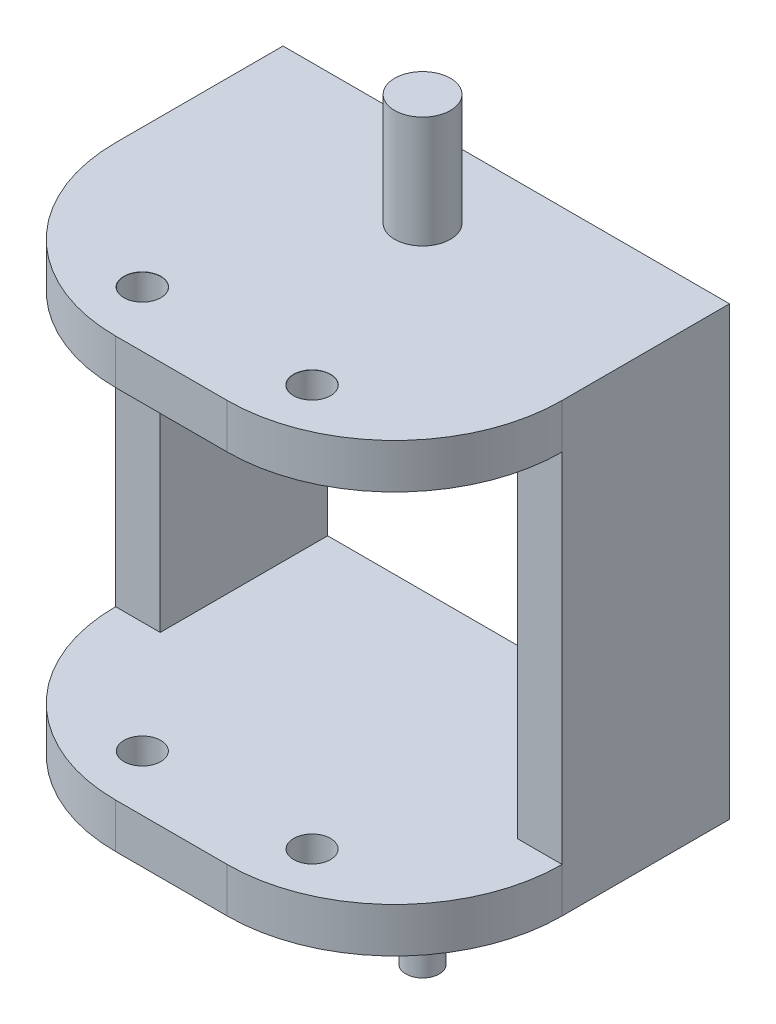
SolidWorks part; units mm, degrees
material "Plastique personnalisé"
ref_plane "Plan de face" through (0, 0, 0) normal (0, 0, 1) x (1, 0, 0)
ref_plane "Plan de dessus" through (0, 0, 0) normal (0, 1, 0) x (1, 0, 0)
ref_plane "Plan de droite" through (0, 0, 0) normal (1, 0, 0) x (0, 0, -1)
sketch "Esquisse1" plane through (0, 0, 0) normal (0, 0, 1) x (1, 0, 0)
  line L1 (40, -40) -> (-40, -40)
  line L2 (40, -40) -> (40, 40)
  line L3 (40, 40) -> (-40, 40)
  line L4 (-40, -40) -> (-40, 40)
  line L5 (40, -40) -> (-40, 40) construction
  line L6 (40, 40) -> (-40, -40) construction
  line L7 (-32, -32) -> (32, -32)
  line L8 (-32, -32) -> (-32, 32)
  line L9 (-32, 32) -> (32, 32)
  line L10 (32, -32) -> (32, 32)
  line L11 (-32, -32) -> (32, 32) construction
  line L12 (-32, 32) -> (32, -32) construction
  point P0 (0, 0)
  point P11 (0, 0)
  dimension "D1" = 8
  dimension "D3" = 80
extrude "Boss.-Extru.1" add sketch "Esquisse1" along normal mid plane 30
sketch "Esquisse2" plane through (0, 0, 0) normal (1, 0, 0) x (0, 0, -1)
  circle A0 centre (0, 0) radius 5
  dimension "D1" = 10
extrude "Enlèv. mat.-Extru.1" [suppressed] cut sketch "Esquisse2" against normal through all both and the other way through all
sketch "Esquisse3" plane through (0, -40, 0) normal (0, -1, 0) x (-1, 0, 0)
  circle A0 centre (0, 0) radius 5
  dimension "D1" = 10
extrude "Boss.-Extru.2" add sketch "Esquisse3" along normal blind 20
mirror "Symétrie1" about plane through (0, 0, 0) normal (0, 1, 0) of "Boss.-Extru.2"
sketch "Esquisse5" plane through (0, -60, 0) normal (0, -1, 0) x (1, 0, 0)
  circle A0 centre (0, 0) radius 3
  circle A1 centre (0, 0) radius 5 construction
  dimension "D1" = 6
extrude "Boss.-Extru.3" add sketch "Esquisse5" along normal blind 15
sketch "Esquisse6" plane through (0, -75, 0) normal (0, -1, 0) x (1, 0, 0)
  line L1 (3, -3) -> (-3, -3)
  line L2 (3, -3) -> (3, -1.8)
  line L3 (3, -1.8) -> (-3, -1.8)
  line L4 (-3, -3) -> (-3, -1.8)
  circle A0 centre (0, 0) radius 3 construction
  dimension "D1" = 1.2
extrude "Enlèv. mat.-Extru.2" cut sketch "Esquisse6" against normal up to surface (15 mm away) contours L1 L4 L3 L2 up to face at (0, -60, -3)
sketch "Esquisse7" plane through (0, 0, 15) normal (0, 0, 1) x (1, 0, 0)
  line L0 (40, 40) -> (-40, 40) construction
  line L1 (40, 32) -> (-40, 32)
  line L2 (40, 32) -> (40, 40)
  line L3 (40, 40) -> (-40, 40)
  line L4 (-40, 32) -> (-40, 40)
  line L6 (32, 32) -> (-32, 32) construction
  point P9 (-29.2155, 40)
  point P11 (0, 0)
extrude "Boss.-Extru.4" add sketch "Esquisse7" along normal blind 30
hole_wizard "Dégagement M61" positions "Esquisse10" profile "Esquisse9" hole size "M6" standard "Ansi Metric" end condition through all
sketch "Esquisse10" plane through (0, 40, 0) normal (0, -1, 0) x (0, 0, -1)
  line L0 (-35, 15.205) -> (-35, -15.205) construction
  line L3 (-35, 0) -> (-45, 0) construction
  line L6 (-45, 40) -> (-45, -40) construction
  point P0 (-35, 15.205)
  point P2 (-35, -15.205)
  point P16 (0, 0)
  point P17 (0, 0)
  point P20 (-45, 0)
  dimension "D1" = 30.41
  dimension "D2" = 10
sketch "Esquisse9" plane through (15.205, 40, 35) normal (1, 0, 0) x (0, 0, 1)
  line L0 (0, 0) -> (0, 115)
  line L1 (0, 115) -> (3.3, 115)
  line L2 (3.3, 115) -> (3.3, 0.025)
  line L3 (3.3, 0.025) -> (3.325, 0)
  line L5 (3.325, 0) -> (0, 0)
  line L6 (-3.3, 0.025) -> (-3.325, 0) construction
  line L11 (0, -6.35) -> (0, 107.95) construction
  dimension "Diamètre du perçage jusqu'au prochain" = 6.6
  dimension "Profondeur du perçage jusqu'au prochain" = 115
  dimension "Diamètre du fraisage entrant" = 6.65
  dimension "Angle du fraisage entrant" = 90
fillet "Congé1" radius 30 2 edges at (40, 36, 45) (-40, 36, 45)
mirror "Symétrie2" about plane through (0, 0, 0) normal (0, 1, 0) of "Boss.-Extru.4", "Dégagement M61", "Congé1"
